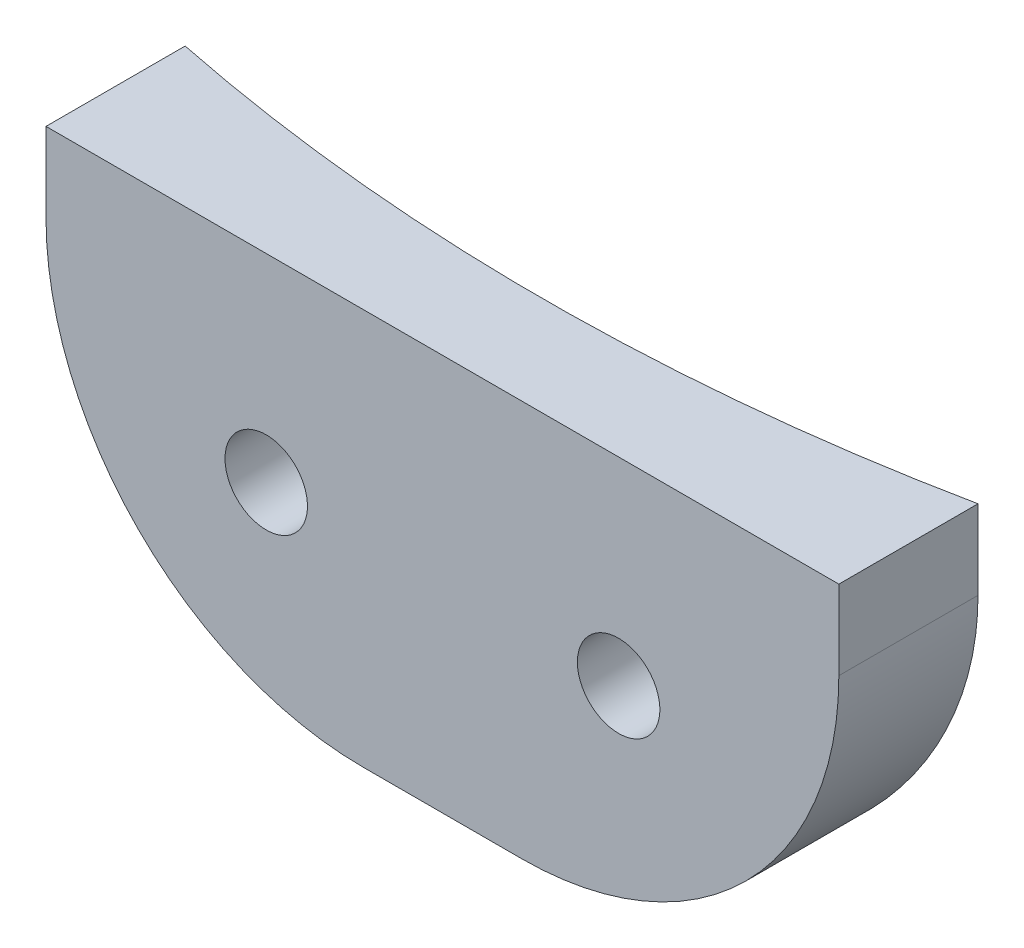
SolidWorks part; units mm, degrees
material "6061 Alloy"
ref_plane "Front Plane" through (0, 0, 0) normal (0, 0, 1) x (1, 0, 0)
ref_plane "Top Plane" through (0, 0, 0) normal (0, 1, 0) x (1, 0, 0)
ref_plane "Right Plane" through (0, 0, 0) normal (1, 0, 0) x (0, 0, -1)
sketch "Sketch1" plane through (0, 0, 0) normal (0, 1, 0) x (1, 0, 0)
  line L0 (-12.7, -62.217) -> (-12.7, -65.4543)
  line L1 (12.7, -62.217) -> (12.7, -65.4543)
  line L2 (-12.7, -66.675) -> (12.7, -66.675)
  line L3 (-12.7, -65.4543) -> (-12.7, -66.675)
  line L4 (12.7, -65.4543) -> (12.7, -66.675)
  circle A0 centre (0, 0) radius 63.5
  circle A1 centre (0, 0) radius 66.675
  dimension "D1" = 127
  dimension "D3" = 12.7
  dimension "D4" = 12.7
  dimension "D2" = 3.175
extrude "Boss-Extrude1" add sketch "Sketch1" along normal blind 12.7 contours L0 A1 L1 A0 | A1 L3 L2 | A1 L2 L4 region at (0, 0, 64.6697) region at (-9.5308, 0, 66.3094) region at (9.5308, 0, 66.3094)
sketch "Sketch2" plane through (0, 0, 0) normal (0, 0, 1) x (1, 0, 0)
  line L0 (0, 12.7) -> (0, 0) construction
  line L5 (-12.7, 0) -> (12.7, 0)
  line L6 (12.7, 0) -> (12.7, 12.7)
  line L7 (12.7, 12.7) -> (-12.7, 12.7)
  line L12 (-12.7, 12.7) -> (-12.7, 0)
  line L13 (-12.7, 0) -> (12.7, 0)
  line L14 (12.7, 0) -> (12.7, 12.7)
  line L15 (12.7, 12.7) -> (-12.7, 12.7)
  line L16 (-12.7, 12.7) -> (-12.7, 0)
  circle A0 centre (-5.6444, 6.35) radius 1.3208
  dimension "D6" = 2.6416
  dimension "D5" = 5.6444
  dimension "D2" = 6.35
extrude "Cut-Extrude1" cut sketch "Sketch2" along normal up to surface (66.675 mm away) contours A0 up to face at (0, 6.35, 66.675)
mirror "Mirror1" about plane through (0, 0, 0) normal (1, 0, 0) of "Cut-Extrude1"
sketch "Sketch3" plane through (0, 0, 0) normal (0, 0, 1) x (1, 0, 0)
  line L0 (-12.7, 12.7) -> (-12.7, 0)
  line L6 (-12.7, 0) -> (0, 0)
  line L7 (12.7, 12.7) -> (12.7, 0)
  line L8 (-2.54, 0) -> (2.54, 0)
  line L9 (12.7, 10.16) -> (12.7, 12.7)
  line L10 (12.7, 12.7) -> (-12.7, 12.7)
  line L11 (-12.7, 12.7) -> (-12.7, 10.16)
  line L12 (12.7, 0) -> (2.54, 0)
  arc A0 (2.54, 0) -> (12.7, 10.16) centre (2.54, 10.16) ccw
  arc A1 (-2.54, 0) -> (-12.7, 10.16) centre (-2.54, 10.16) cw
  dimension "D2" = 10.16
  dimension "D6" = 2.54
  dimension "D1" = 12.7
  dimension "D3" = 12.7
  dimension "D4" = 2.54
  dimension "D5" = 2.54
  dimension "D7" = 2.54
  dimension "D8" = 2.54
  dimension "D9" = 10.16
extrude "Cut-Extrude2" cut sketch "Sketch3" along normal up to surface (66.675 mm away) contours L6 A1 L0 | A0 L12 L7 region at (-10.4306, 2.2694, 0) region at (10.4306, 2.2694, 0) up to face at (4.3236, 6.35, 66.675)
equation "\"Middle Coupler Inner Daimeter\"= 4.5in"
equation "\"Middle Coupler  Wall Thickness\" = 0.25in"
equation "\"Middle Coupler Bottom Thickness\"= 0.2in"
equation "\"Bearing Rail Offset\"= 0.45in"
equation "\"3-56 UNF Tap\"= 0.089in"
equation "\"3-56 UNF Clearance\"= 0.104in"
equation "\"Ball Bearing Distance\"= 0.03in"
equation "\"TCA Outer Diameter\" = 6.625in"
equation "\"D1@Sketch1\"=\"Middle Coupler Inner Daimeter\"+0.5"
equation "\"D2@Sketch1\"=1/8"
equation "\"D3@Sketch1\"=0.5"
equation "\"D4@Sketch1\"=\"D3@Sketch1\""
equation "\"D6@Sketch2\"=\"3-48 Clearance\""
equation "\"Interstage Aeroframe Wall Thickness\" = 0.072in"
equation "\"Compression Spring OD\"= 0.42in"
equation "\"10-24 Tap\"= 0.157in"
equation "\"10-24 Clearance\"= 0.196in"
equation "\"Lower Stage Fuselage Wall Thickness\" = 0.25in"
equation "\"6-32 Tap\" = 0.107in"
equation "\"1/4-20 Tap\" = 0.201in"
equation "\"3-48 Tap\"= 0.079in"
equation "\"3-48 Clearance\" = 0.104in"
equation "\"6-32 Clearance\" = 0.144"
equation "\"12-24 Tap\" = 0.177in"
